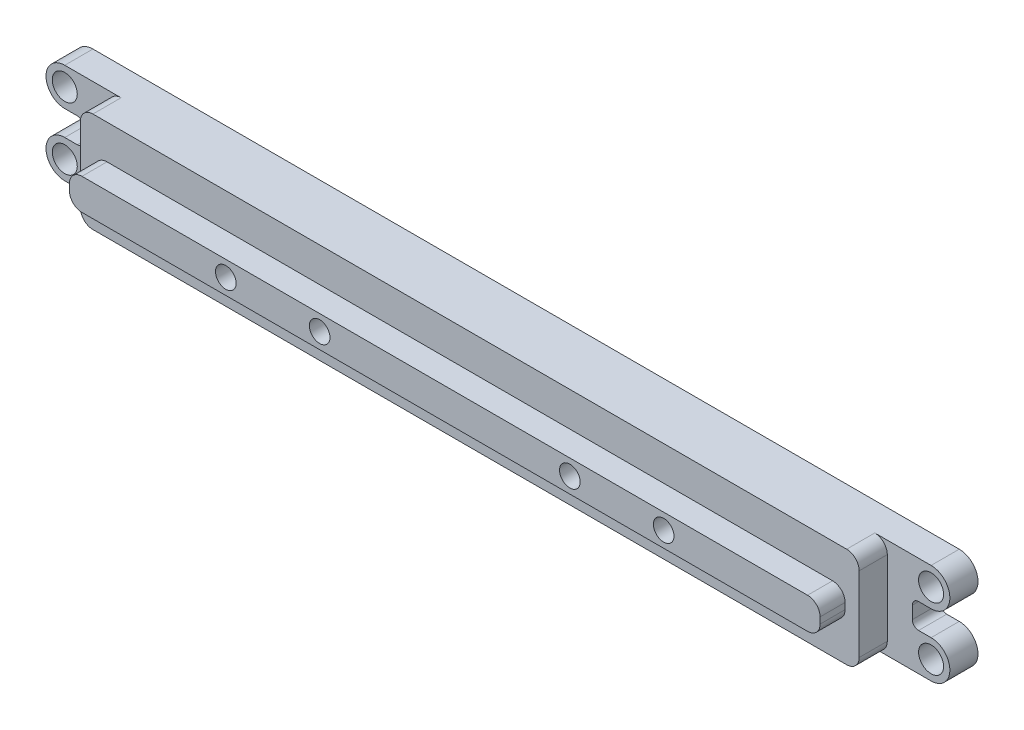
SolidWorks part; units mm, degrees
ref_plane "前视基准面" through (0, 0, 0) normal (0, 0, 1) x (1, 0, 0)
ref_plane "上视基准面" through (0, 0, 0) normal (0, 1, 0) x (1, 0, 0)
ref_plane "右视基准面" through (0, 0, 0) normal (1, 0, 0) x (0, 0, -1)
other "Configuration Table"
sketch "草图1" plane through (0, 0, 0) normal (0, 0, 1) x (1, 0, 0)
  line L0 (-69.25, 8) -> (-66.25, 8)
  line L1 (-69.25, -5) -> (69.25, -5) construction
  line L2 (-69.25, -5) -> (-69.25, 5) construction
  line L3 (-69.25, 5) -> (69.25, 5) construction
  line L4 (69.25, -5) -> (69.25, 5) construction
  line L5 (-69.25, -5) -> (69.25, 5) construction
  line L6 (-69.25, 5) -> (69.25, -5) construction
  line L7 (-66.25, -8) -> (66.25, -8)
  line L8 (-66.25, -8) -> (-66.25, 8)
  line L9 (-66.25, 8) -> (66.25, 8)
  line L10 (66.25, -8) -> (66.25, 8)
  line L11 (-66.25, -8) -> (66.25, 8) construction
  line L12 (-66.25, 8) -> (66.25, -8) construction
  line L13 (-69.25, 2) -> (-66.25, 2)
  line L14 (-75.2024, 0) -> (0, 0) construction
  line L15 (0, 0) -> (0, 29.0669) construction
  line L16 (-69.25, -2) -> (-66.25, -2)
  line L17 (-69.25, -8) -> (-66.25, -8)
  line L18 (69.25, -8) -> (66.25, -8)
  line L19 (69.25, -2) -> (66.25, -2)
  line L20 (69.25, 2) -> (66.25, 2)
  line L21 (69.25, 8) -> (66.25, 8)
  circle A0 centre (-69.25, 5) radius 2
  circle A1 centre (-69.25, -5) radius 2
  circle A2 centre (69.25, 5) radius 2
  circle A3 centre (69.25, -5) radius 2
  arc A4 (-69.25, 8) -> (-69.25, 2) centre (-69.25, 5) ccw
  arc A5 (-69.25, -8) -> (-69.25, -2) centre (-69.25, -5) cw
  arc A6 (69.25, -8) -> (69.25, -2) centre (69.25, -5) ccw
  arc A7 (69.25, 8) -> (69.25, 2) centre (69.25, 5) cw
  point P0 (0, 0)
  point P10 (0, 0)
  dimension "D3" = 4
  dimension "D1" = 138.5
  dimension "D2" = 10
  dimension "D4" = 3
  dimension "D5" = 3
extrude "凸台-拉伸1" add sketch "草图1" along normal blind 4.5 contours L7 L10 L9 L8 | L0 A4 L13 L8 A0 | A5 L17 L8 L16 A1 | A7 L21 L10 L20 A2 | L18 A6 L19 L10 A3 region at (-67.75, 7.9151, 0) region at (0, 0, 0) region at (67.75, 7.9151, 0) region at (-66.3349, -5, 0) region at (67.75, -2.0849, 0)
fillet "圆角1" radius 1 4 edges at (-66.25, -2, 2.25) (-66.25, 2, 2.25) (66.25, 2, 2.25) (66.25, -2, 2.25)
sketch "草图3" plane through (0, 0, 0) normal (1, 0, 0) x (0, 0, -1)
  line L0 (-4.5, 8) -> (-4.5, 4.5)
  line L2 (-4.5, 4.5) -> (-1, 8)
  line L3 (-4.5, 8) -> (0, 8) construction
  line L4 (-1, 8) -> (-4.5, 8)
  arc A0 (-4.5, 4.5) -> (-1, 8) centre (-2.75, 6.25) ccw
  dimension "D1" = 3.5
extrude "切除-拉伸2" [suppressed] cut sketch "草图3" against normal blind 60 and the other way blind 60 contours L2 L4 L0 | L2 A0
fillet "圆角2" [suppressed] radius 1
sketch "草图5" plane through (0, 0, 4.5) normal (0, 0, 1) x (1, 0, 0)
  line L0 (-69.25, 8) -> (69.25, 8) construction
  line L1 (62.25, -8) -> (-62.25, -8)
  line L2 (62.25, -8) -> (62.25, 8)
  line L3 (62.25, 8) -> (-62.25, 8)
  line L4 (-62.25, -8) -> (-62.25, 8)
  line L5 (62.25, -8) -> (-62.25, 8) construction
  line L6 (62.25, 8) -> (-62.25, -8) construction
  line L7 (-66.25, -1) -> (-66.25, 1) construction
  point P0 (0, 0)
  dimension "D1" = 4
extrude "凸台-拉伸2" add sketch "草图5" along normal blind 4.5
sketch "草图6" plane through (0, 0, 9) normal (0, 0, 1) x (1, 0, 0)
  line L1 (60, -2.5) -> (-60, -2.5)
  line L2 (60, -2.5) -> (60, 2.5)
  line L3 (60, 2.5) -> (-60, 2.5)
  line L4 (-60, -2.5) -> (-60, 2.5)
  line L5 (60, -2.5) -> (-60, 2.5) construction
  line L6 (60, 2.5) -> (-60, -2.5) construction
  point P0 (0, 0)
  dimension "D1" = 120
  dimension "D2" = 5
extrude "凸台-拉伸3" add sketch "草图6" along normal blind 4
sketch "草图2" plane through (0, 0, 4.5) normal (0, 0, 1) x (1, 0, 0)
  line L1 (0, 0) -> (0, 44.3614) construction
  line L2 (20, 0) -> (35, 0) construction
  line L3 (-69.25, -8) -> (-62.25, -8) construction
  line L4 (-20, 0) -> (-35, 0) construction
  circle A0 centre (35, 0) radius 1.65
  circle A1 centre (20, 0) radius 1.65
  circle A2 centre (-20, 0) radius 1.65
  circle A3 centre (-35, 0) radius 1.65
  dimension "D4" = 3.3
  dimension "D1" = 15
  dimension "D2" = 8
  dimension "D3" = 20
extrude "切除-拉伸1" cut sketch "草图2" against normal through all and the other way through all
fillet "圆角3" radius 2 8 edges at (-62.25, 8, 6.75) (62.25, 8, 6.75) (62.25, -8, 6.75) (-62.25, -8, 6.75) (-60, -2.5, 11) (60, -2.5, 11) (60, 2.5, 11) (-60, 2.5, 11)
